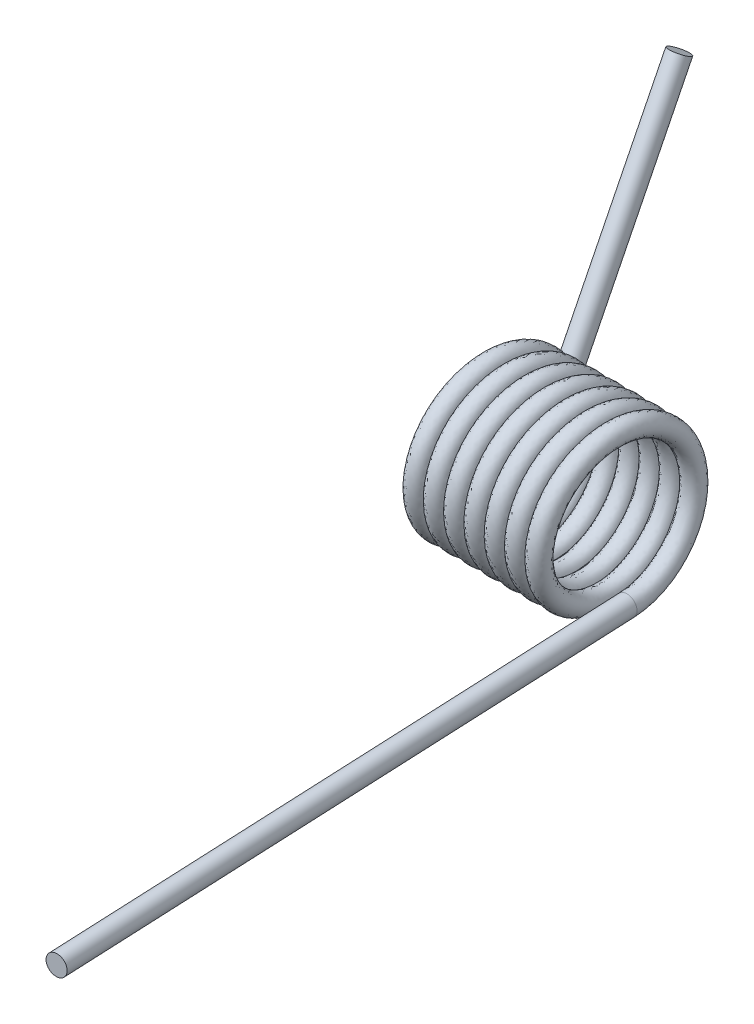
SolidWorks part; units mm, degrees
ref_plane "Front" through (0, 0, 0) normal (0, 0, 1) x (1, 0, 0)
ref_plane "Top" through (0, 0, 0) normal (0, 1, 0) x (1, 0, 0)
ref_plane "Right" through (0, 0, 0) normal (1, 0, 0) x (0, 0, -1)
sketch "Sketch1" plane through (0, 0, 0) normal (1, 0, 0) x (0, 0, -1)
  line L0 (0, -10.5664) -> (0, -13.9954) construction
  line L1 (12.1204, -6.9977) -> (62.9204, 80.9905) construction
  line L2 (0, -13.9954) -> (-101.6, -13.9954) construction
  line L3 (0, 0) -> (13.9954, 0) construction
  line L4 (0, 0) -> (12.1204, -6.9977) construction
  line L5 (-101.6, -13.9954) -> (-101.6, -10.5664) construction
  line L6 (-101.6, -10.5664) -> (0, -10.5664) construction
  line L7 (62.9204, 80.9905) -> (59.9508, 82.705) construction
  line L8 (59.9508, 82.705) -> (9.1508, -5.2832) construction
  circle A0 centre (0, 0) radius 13.9954 construction
  circle A1 centre (0, 0) radius 8.4582 construction
  circle A2 centre (0, 0) radius 12.2809 construction
  point P7 (0, -12.2809)
  point P10 (0, 13.9954)
  dimension "OD" = 27.9908
  dimension "For Shaft Diameter" = 16.9164
  dimension "Wire Diameter" = 3.429
  dimension "Leg Length" = 101.6
  dimension "Deflection Angle" = 120
sketch "Sketch2" plane through (0, 0, 0) normal (1, 0, 0) x (0, 0, -1)
  circle A0 centre (0, 0) radius 12.2809 construction
  circle A2 centre (0, 0) radius 12.2809
curve "Helix/Spiral1" pitch 3.4544 height 24.7565 radius 12.2809 left hand yes centre (0, 0, 0) axis (-1, 0, 0) start towards (0, 0, -1)
ref_plane "Plane1" through (0, -12.2809, 0) normal (-0.0447, 0, -0.999) x (0.9987, -0.0232, -0.0447)
sketch "Sketch3" plane through (0, -12.2809, 0) normal (-0.0447, 0, -0.999) x (0.9987, -0.0232, -0.0447)
  circle A0 centre (0, 0) radius 1.7145
  dimension "D1" = 3.429
sweep "Sweep1" add profiles "Sketch3" path "Helix/Spiral1"
sketch "Sketch4" plane through (0, 0, 0) normal (0.0447, 0, 0.999) x (-0.9987, 0.0232, 0.0447)
  circle A1 centre (-0.2854, 12.2776) radius 1.7145
  circle A2 centre (-0.2854, 12.2776) radius 1.7145
  dimension "D1" = 0
extrude "Extrude1" add sketch "Sketch4" along normal blind 101.6
sketch "Sketch5" plane through (-0.0495, 0.9579, -0.553) normal (-0.0447, 0.8652, -0.4995) x (0.999, 0.0387, -0.0223)
  circle A1 centre (-24.7322, 12.2801) radius 1.7145
  circle A2 centre (-24.7322, 12.2801) radius 1.7145
  dimension "D1" = 0
extrude "Extrude2" add sketch "Sketch5" along normal blind 50.8
sketch "Sketch6" plane through (0, 0, 0) normal (1, 0, 0) x (0, 0, -1)
  circle A2 centre (0, 0) radius 10.5664 construction
equation "\"D4@Helix/Spiral1\" = \"Wire Diameter@Sketch1\" + .001"
equation "\"D1@Sketch3\"=\"Wire Diameter@Sketch1\""
equation "\"Leg Length@Extrude1\"=\"Leg Length@Sketch1\""
